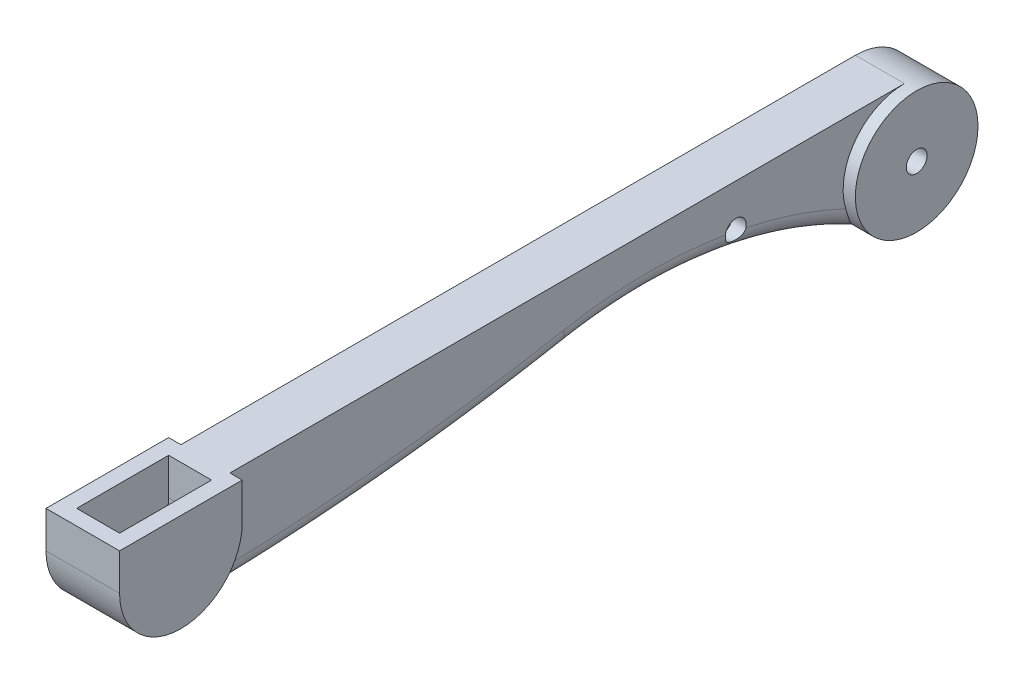
SolidWorks part; units mm, degrees
ref_plane "Front Plane" through (0, 0, 0) normal (0, 0, 1) x (1, 0, 0)
ref_plane "Top Plane" through (0, 0, 0) normal (0, 1, 0) x (1, 0, 0)
ref_plane "Right Plane" through (0, 0, 0) normal (1, 0, 0) x (0, 0, -1)
sketch "Sketch1" plane through (0, 0, 0) normal (1, 0, 0) x (0, 0, -1)
  line L0 (0, 10) -> (-110, 10)
  line L1 (-130, 10) -> (-130, 4)
  line L3 (-130, 10) -> (-120, 10)
  line L4 (-120, 10) -> (-110, 10)
  arc A0 (0, 10) -> (-5.0267, -8.6448) centre (0, 0) cw
  arc A2 (-130, 4) -> (-120, -6) centre (-120, 4) ccw
  arc A3 (-120, -6) -> (-55, 0) centre (-120, 349.0833) ccw
  arc A4 (-55, 0) -> (-5.0267, -8.6448) centre (-41.6595, -71.6456) cw
  circle A5 centre (0, 0) radius 1.7
  point P0 (0, 0)
  point P19 (-55, 10)
  dimension "D1" = 10
  dimension "D4" = 20
  dimension "D5" = 3.4
  dimension "D6" = 10
  dimension "D2" = 130
  dimension "D3" = 6
extrude "Boss-Extrude1" add sketch "Sketch1" along normal mid plane 8
sketch "Sketch2" plane through (0, 0, 0) normal (1, 0, 0) x (0, 0, -1)
  line L4 (-130, 4) -> (-130, 10)
  line L5 (-130, 10) -> (-110, 10)
  line L6 (-110, 10) -> (-110, 4)
  arc A1 (-130, 4) -> (-110, 4) centre (-120, 4) ccw
extrude "Boss-Extrude2" add sketch "Sketch2" along normal mid plane 12
sketch "Sketch3" plane through (0, 0, 0) normal (1, 0, 0) x (0, 0, -1)
  circle A0 centre (0, 0) radius 10
extrude "Boss-Extrude3" add sketch "Sketch3" along normal blind 6
fillet "Fillet2" radius 3 4 edges at (4, -4.4968, 87.3618) (-4, -4.4968, 87.3618) (4, 0.1649, 29.2371) (-4, 0.1649, 29.2371) tangent propagation no
extrude "Cut-Extrude1" cut sketch "Sketch1<2>" along normal through all contours A5 region at (0, 0, 0)
sketch "Sketch1<2>" plane through (0, 0, 0) normal (1, 0, 0) x (0, 0, -1) same geometry as "Sketch1"
sketch "Sketch5" plane through (0, 0, 0) normal (1, 0, 0) x (0, 0, -1)
  line L0 (0, 10) -> (-110, 10) construction
  line L1 (-32.1985, 4.7101) -> (-33.6262, 0.7873)
  line L2 (-22.6704, 4.2941) -> (-21.0528, -1.7426)
  line L3 (-33.6262, 0.7873) -> (-21.0528, -1.7426)
  line L4 (-27.5, -7.2828) -> (-27.5, 15.3934) construction
  arc A0 (-32.1985, 4.7101) -> (-22.6704, 4.2941) centre (-27.5, 3) cw
  arc A1 (-5.0267, -8.6448) -> (-55, 0) centre (-41.6595, -71.6456) ccw construction
  point P0 (-27.5, 3)
  point P13 (-27.5, 3)
  dimension "D3" = 5
  dimension "D1" = 27.5
  dimension "D2" = 7
  dimension "D4" = 15
  dimension "D5" = 20
extrude "Cut-Extrude3" cut sketch "Sketch5" against normal mid plane 3.4
sketch "Sketch9" plane through (0, 0, 0) normal (1, 0, 0) x (0, 0, -1)
  circle A0 centre (-27.5, 3) radius 1.7
  dimension "D1" = 3.4
extrude "Cut-Extrude4" cut sketch "Sketch9" against normal through all both and the other way through all
sketch "Sketch11" plane through (0, 0, 0) normal (1, 0, 0) x (0, 0, -1)
  line L0 (-127.5, 10) -> (-112.5, 10)
  line L1 (-112.5, 10) -> (-112.5, 4)
  line L2 (-127.5, 4) -> (-127.5, 10)
  line L3 (-120, 4) -> (-120, -4)
  line L4 (-120, -4) -> (-115.6782, -1.5048)
  line L5 (-120, -4) -> (-124.3218, -1.5048)
  line L6 (-127.5, 4) -> (-112.5, 4) construction
  arc A1 (-124.3218, -1.5048) -> (-127.5, 4) centre (-121.1436, 4) cw
  arc A2 (-115.6782, -1.5048) -> (-112.5, 4) centre (-118.8564, 4) ccw
  point P4 (-120, 10)
  dimension "D1" = 60
  dimension "D2" = 60
  dimension "D3" = 2
  dimension "D4" = 2.5
extrude "Cut-Extrude5" cut sketch "Sketch11" against normal mid plane 7 contours L5 A1 L2 L0 L1 A2 L4
ref_plane "Plane1" through (0, 9, 0) normal (0, -1, 0) x (-1, 0, 0)
sketch "Sketch12" plane through (0, 9, 0) normal (0, -1, 0) x (-1, 0, 0)
  line L0 (0, 0) -> (0, -110) construction
  circle A0 centre (0, -107.0221) radius 2.5
  dimension "D1" = 5
extrude "Cut-Extrude6" cut sketch "Sketch12" along normal through all contours A0
pattern_linear "LPattern1" count 13 spacing 8 along (0, 0, -1) skipping (9, 0), (10, 0), (11, 0) of "Cut-Extrude6"
